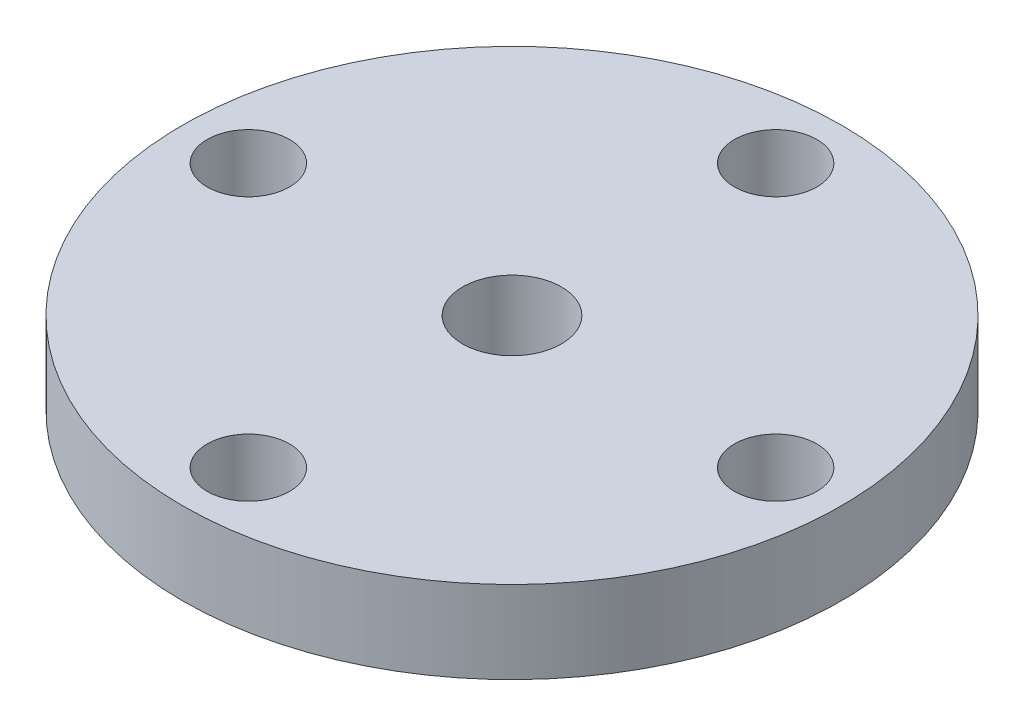
SolidWorks part; units mm, degrees
material "ABS"
ref_plane "Front Plane" through (0, 0, 0) normal (0, 0, 1) x (1, 0, 0)
ref_plane "Top Plane" through (0, 0, 0) normal (0, 1, 0) x (1, 0, 0)
ref_plane "Right Plane" through (0, 0, 0) normal (1, 0, 0) x (0, 0, -1)
sketch "Sketch1" plane through (0, 0, 0) normal (0, 1, 0) x (1, 0, 0)
  line L0 (0, 24.1217) -> (0, -25.5168) construction
  line L1 (-33.1168, 0) -> (38.4772, 0) construction
  circle A0 centre (0, 0) radius 10
  circle A1 centre (0, 0) radius 1.5
  circle A2 centre (0, 8) radius 1.25
  circle A3 centre (0, 0) radius 10
  circle A4 centre (8, 0) radius 1.25
  circle A5 centre (0, 0) radius 10
  circle A6 centre (0, -8) radius 1.25
  circle A7 centre (0, 0) radius 10
  circle A8 centre (-8, 0) radius 1.25
  point P22 (0, 0)
  dimension "D1" = 20
  dimension "D2" = 3
  dimension "D3" = 2.5
  dimension "D5" = 8
  dimension "D4" = 4
extrude "Boss-Extrude1" add sketch "Sketch1" along normal blind 2.5 contours A0 A8 A6 A4 A2 A1 region at (-9.7172, 0, 0)
cosmetic thread "Cosmetic Thread1" parameters "D1"=2.4999, "D2"=3
cosmetic thread "Cosmetic Thread2" parameters "D1"=2.4999, "D2"=3
cosmetic thread "Cosmetic Thread3" parameters "D1"=2.4999, "D2"=3
cosmetic thread "Cosmetic Thread4" parameters "D1"=2.4999, "D2"=3
